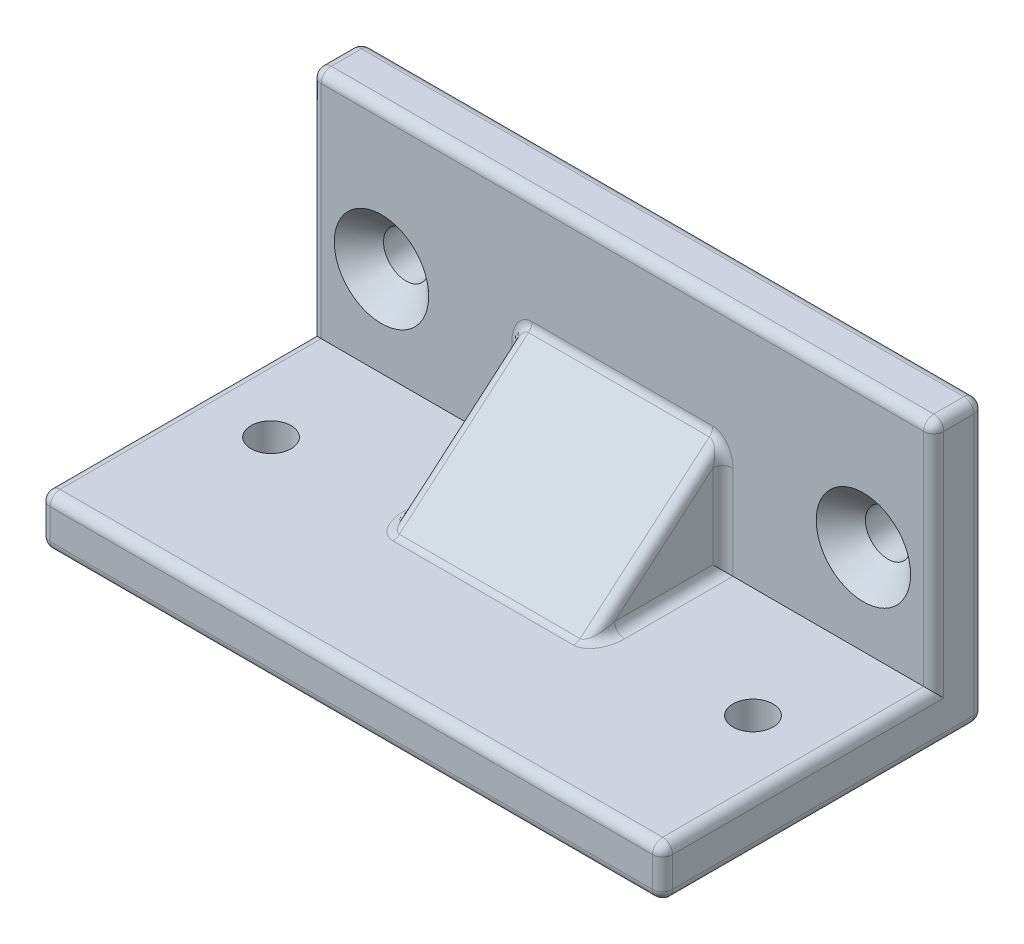
SolidWorks part; units mm, degrees
ref_plane "Front Plane" through (0, 0, 0) normal (0, 0, 1) x (1, 0, 0)
ref_plane "Top Plane" through (0, 0, 0) normal (0, 1, 0) x (1, 0, 0)
ref_plane "Right Plane" through (0, 0, 0) normal (1, 0, 0) x (0, 0, -1)
sketch "Skizze4" plane through (0, 0, 0) normal (0, 1, 0) x (1, 0, 0)
  line L0 (0, -3) -> (0, -35) construction
  line L2 (0, -35) -> (-35, -35) construction
  line L3 (-35, -35) -> (-35, -3) construction
  line L4 (-35, -3) -> (35, -3) construction
  line L5 (35, -3) -> (35, -35) construction
  line L6 (35, -35) -> (0, -35) construction
  line L7 (-24, -19) -> (0, -19) construction
  line L8 (0, -19) -> (24, -19) construction
  circle A0 centre (-24, -19) radius 2
  circle A1 centre (24, -19) radius 2
  dimension "D3" = 4
  dimension "D1" = 70
  dimension "D2" = 32
  dimension "D4" = 24
sketch "Skizze1" plane through (0, 0, 0) normal (0, 0, 1) x (1, 0, 0)
  line L0 (-37.5522, 28) -> (-43.5522, 28) construction
  line L1 (-37.5522, 28) -> (37.5522, 28) construction
  line L3 (-37.5522, 0) -> (37.5522, 0) construction
  line L5 (-43.5522, 28) -> (-43.5522, 0) construction
  line L6 (-43.5522, 0) -> (-37.5522, 0) construction
  line L7 (37.5522, 28) -> (43.5522, 28) construction
  line L8 (43.5522, 28) -> (43.5522, 0) construction
  line L9 (43.5522, 0) -> (37.5522, 0) construction
  line L10 (0, 0) -> (0, 28) construction
  line L11 (-24, 14) -> (0, 14) construction
  line L12 (0, 14) -> (24, 14) construction
  circle A0 centre (-24, 14) radius 2
  circle A1 centre (24, 14) radius 2
  point P11 (0, 0)
  dimension "D5" = 4
  dimension "D1" = 75.1044
  dimension "D2" = 28
  dimension "D3" = 6
  dimension "D4" = 24
sketch "Sketch2" plane through (0, 0, 0) normal (1, 0, 0) x (0, 0, -1)
  line L0 (-35, 0) -> (-35, 5)
  line L1 (-3, 0) -> (-35, 0) construction
  line L2 (-35, 5) -> (-8, 5)
  line L3 (-3, 5) -> (-3, 0)
  line L4 (-3, 5) -> (-3, 28)
  line L5 (-3, 28) -> (-8, 28)
  line L6 (-8, 28) -> (-8, 5)
  line L7 (-3, 28) -> (0, 28) construction
  line L8 (0, 28) -> (0, 0) construction
  line L9 (0, 28) -> (0, 0) construction
  line L10 (-35, 0) -> (-3, 0)
  dimension "D1" = 5
  dimension "D2" = 5
  dimension "D3" = 28
extrude "Boss-Extrude2" add sketch "Sketch2" along normal blind 31 and the other way blind 31 contours L6 L2 L0 L10 L3 L4 L5
sketch "Sketch3" plane through (0, 0, 0) normal (1, 0, 0) x (0, 0, -1)
  line L0 (-21.5, 5) -> (-8, 16.5)
  line L1 (-35, 5) -> (-8, 5) construction
  line L2 (-8, 28) -> (-8, 5) construction
  line L3 (-8, 16.5) -> (-8, 5)
  line L4 (-8, 5) -> (-21.5, 5)
extrude "Boss-Extrude3" add sketch "Sketch3" along normal blind 10 and the other way blind 10
hole_wizard "CSK for M4 Flat Head Machine Screw1" positions "Sketch4" profile "Sketch5" countersink size "M4" standard "ANSI Metric" end condition through all
sketch "Sketch4" plane through (0, 0, 8) normal (0, 0, 1) x (1, 0, 0)
  point P0 (-24, 14)
  point P3 (24, 14)
sketch "Sketch5" plane through (-24, 14, 8) normal (1, 0, 0) x (0, -1, 0)
  line L0 (0, 0) -> (0, 5)
  line L1 (0, 5) -> (2.25, 5)
  line L2 (2.25, 5) -> (2.25, 2.45)
  line L3 (2.25, 2.45) -> (4.7, 0)
  line L5 (4.7, 0) -> (0, 0)
  line L6 (-2.25, 2.45) -> (-4.7, 0) construction
  line L11 (0, -6.35) -> (0, 107.95) construction
  dimension "Thru Hole Dia." = 4.5
  dimension "Thru Hole Depth" = 5
  dimension "Near C'Sink Dia." = 9.4
  dimension "Near C'Sink Angle" = 90
extrude "Cut-Extrude1" cut sketch "Skizze4" along normal up to surface (5 mm away) contours A0 | A1 up to face at (0, 5, 18.125)
fillet "Fillet2" radius 1 25 edges at (0, 0, 35) (0, 5, 35) (-31, 16.5, 8) (-31, 5, 21.5) (-31, 2.5, 35) (-31, 0, 19) (-31, 14, 3) (0, 28, 8) (-31, 28, 5.5) (0, 28, 3) (31, 14, 3) (31, 0, 19) (31, 2.5, 35) (31, 5, 21.5) (31, 16.5, 8) (31, 28, 5.5) (0, 0, 3) (-10, 10.75, 8) (-10, 5, 14.75) (10, 10.75, 8) (10, 5, 14.75) (-10, 10.75, 14.75) (0, 16.5, 8) (10, 10.75, 14.75) (0, 5, 21.5)
